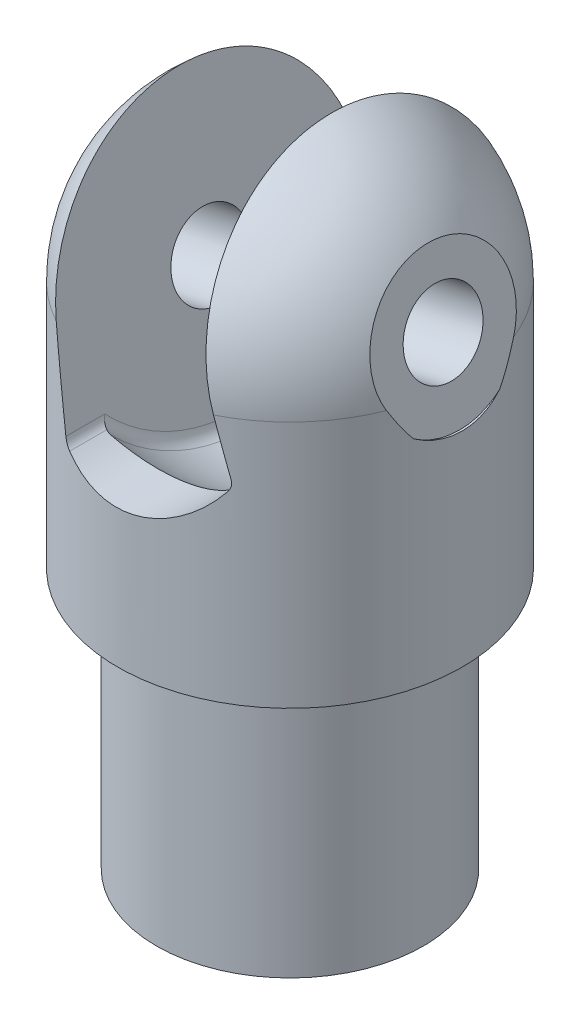
SolidWorks part; units mm, degrees
ref_plane "Front Plane" through (0, 0, 0) normal (0, 0, 1) x (1, 0, 0)
ref_plane "Top Plane" through (0, 0, 0) normal (0, 1, 0) x (1, 0, 0)
ref_plane "Right Plane" through (0, 0, 0) normal (1, 0, 0) x (0, 0, -1)
sketch "Sketch1" plane through (0, 0, 0) normal (0, 1, 0) x (1, 0, 0)
  circle A0 centre (0, 0) radius 12.9921
extrude "Boss-Extrude1" add sketch "Sketch1" along normal blind 25.4 contours A0
sketch "Sketch2" plane through (0, 0, 0) normal (1, 0, 0) x (0, 0, -1)
  line L0 (-16.764, 25.4) -> (-16.764, 49.53)
  line L1 (0, 25.4) -> (-16.764, 25.4)
  line L4 (12.9921, 25.4) -> (-12.9921, 25.4) construction
  line L5 (0, 14.2913) -> (0, -14.2913) construction
  line L6 (0, 25.4) -> (0, 66.294)
  arc A0 (0, 66.294) -> (-16.764, 49.53) centre (0, 49.53) ccw
  dimension "D1" = 33.528
  dimension "D2" = 24.13
revolve "Revolve1" add sketch "Sketch2" angle 360 about L6
ref_plane "Plane2" through (0, 49.53, 0) normal (0, -1, 0) x (-1, 0, 0)
ref_axis "Axis1" through (0, 49.53, 23.7) along (0, 0, -1)
ref_plane "Plane3" through (-10.0728, 47.389, 0) normal (0.2079, -0.9781, 0) x (0, 0, -1)
ref_plane "Plane4" through (10.0728, 2.141, 0) normal (-0.9781, -0.2079, 0) x (0, 0, -1)
sketch "Sketch3" plane through (-10.3665, 98.3003, 0) normal (-0.9781, -0.2079, 0) x (0, 0, -1)
  line L1 (-23.7, 49.8599) -> (13.1808, 49.8599) construction
  line L2 (0, 49.8599) -> (0, 73.4626) construction
  circle A2 centre (0, 49.8599) radius 3.81
  dimension "D1" = 7.62
extrude "Cut-Extrude1" cut sketch "Sketch3" against normal through all both and the other way through all
ref_axis "Axis2" through (17.4875, 53.2471, 0) along (-0.9781, -0.2079, 0)
sketch "Sketch10" plane through (0, 0, 0) normal (0, 0, 1) x (1, 0, 0)
  line L0 (17.4875, 53.2471) -> (-17.6069, 45.7875) construction
  line L1 (-7.7019, 47.8929) -> (7.205, 51.0615)
  point P5 (-0.2484, 49.4772)
  dimension "D1" = 15.24
  dimension "D2" = 0.254
sketch "Sketch11" plane through (0, 0, 0) normal (0, 0, 1) x (1, 0, 0)
  line L2 (-7.7019, 47.8929) -> (7.205, 51.0615) construction
  line L3 (-7.7019, 47.8929) -> (-11.163, 64.1758)
  line L4 (7.205, 51.0615) -> (3.696, 67.5703)
  line L5 (-7.7019, 47.8929) -> (7.205, 51.0615)
  arc A0 (3.696, 67.5703) -> (-11.163, 64.1758) centre (0, 49.53) ccw
  arc A1 (15.1764, 56.651) -> (-16.7607, 49.8625) centre (0, 49.53) ccw construction
  dimension "D1" = 18.415
revolve "Cut-Revolve10" cut sketch "Sketch11" angle 180 about axis through (17.4875, 53.2471, 0) along (-0.9781, -0.2079, 0) other way angle 90
sketch "Sketch13" plane through (0, 0, 0) normal (0, 0, 1) x (1, 0, 0)
  line L0 (-8.4941, 51.6196) -> (6.4129, 54.7882)
  line L1 (-8.0499, 49.53) -> (-10.779, 62.3692) construction
  line L2 (4.0741, 65.7914) -> (7.5306, 49.53) construction
  line L3 (-7.7019, 47.8929) -> (7.205, 51.0615) construction
  line L4 (-8.4941, 51.6196) -> (-11.9796, 68.0178)
  line L5 (6.4129, 54.7882) -> (2.9274, 71.1864)
  arc A0 (2.9274, 71.1864) -> (-11.9796, 68.0178) centre (-1.0406, 53.2039) ccw
  dimension "D1" = 3.81
  dimension "D2" = 36.83
revolve "Cut-Revolve11" cut sketch "Sketch13" angle 360 about L0
sketch "Sketch14" plane through (0, 0, 0) normal (0, 0, 1) x (1, 0, 0)
  line L0 (-7.7019, 47.8929) -> (7.205, 51.0615) construction
  line L1 (-7.7019, 47.8929) -> (-6.1497, 40.59)
  line L2 (7.205, 51.0615) -> (8.7573, 43.7586)
  line L3 (-7.7019, 47.8929) -> (7.205, 51.0615)
  arc A0 (-6.1497, 40.59) -> (8.7573, 43.7586) centre (-0.2484, 49.4772) ccw
  dimension "D1" = 21.336
extrude "Cut-Extrude4" cut sketch "Sketch14" along normal blind 32.004
fillet "Fillet1" radius 1.27 8 edges at (-4.84, 34.4287, -9.3615) (-4.6247, 33.4157, 0) (-5.3066, 36.6236, 6.7827) (-6.1497, 40.59, 14.0004) (8.7573, 43.7586, 13.3502) (9.6004, 39.7921, 6.7827) (10.3063, 36.4714, 0) (10.2986, 36.5075, -7.9665)
ref_plane "Plane5" through (-4.8341, -1.0275, 0) normal (-0.9781, -0.2079, 0) x (0, 0, -1)
sketch "Sketch15" plane through (-4.8341, -1.0275, 0) normal (-0.9781, -0.2079, 0) x (0, 0, -1)
  circle A0 centre (0, -48.4477) radius 7.62
  dimension "D1" = 15.24
extrude "Cut-Extrude5" cut sketch "Sketch15" along normal blind 10.16
mirror "Mirror1" about plane through (10.0728, 2.141, 0) normal (-0.9781, -0.2079, 0) of "Cut-Extrude5"
